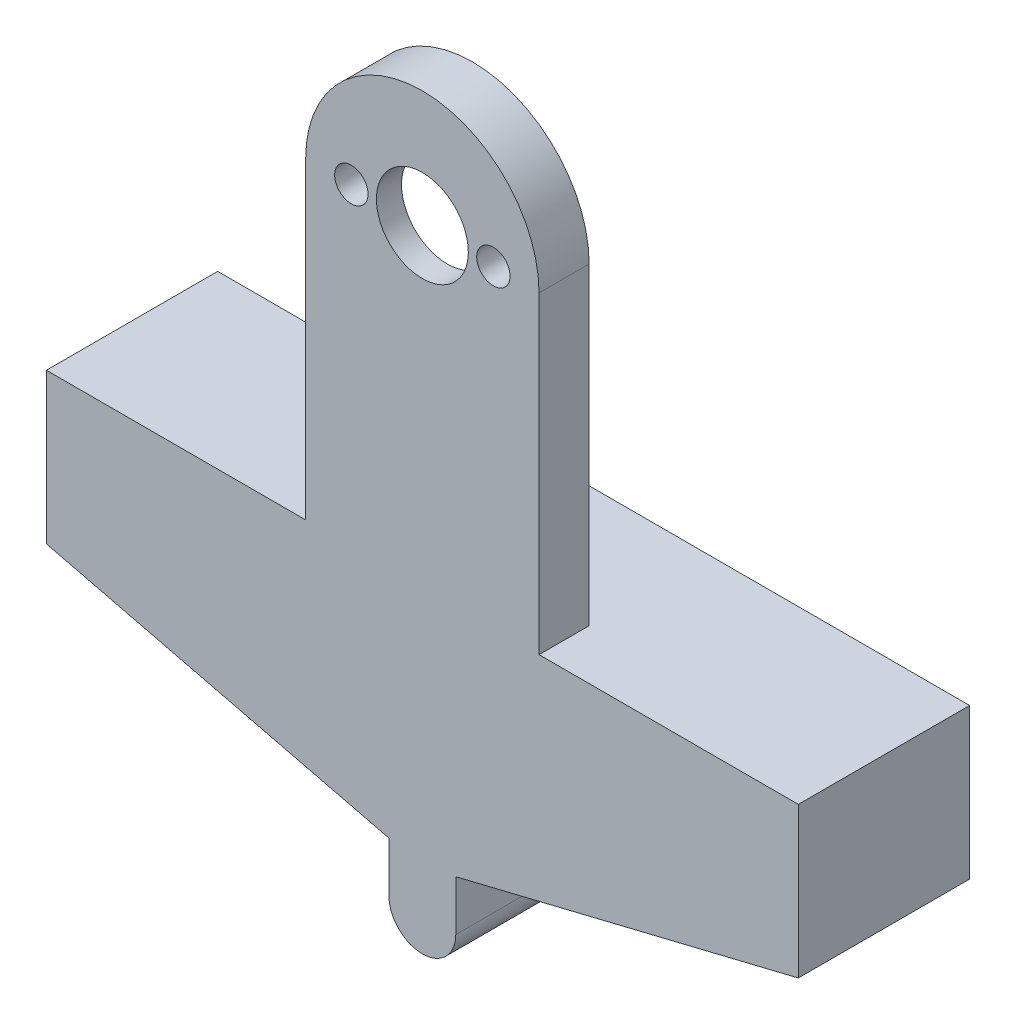
SolidWorks part; units mm, degrees
ref_plane "Front Plane" through (0, 0, 0) normal (0, 0, 1) x (1, 0, 0)
ref_plane "Top Plane" through (0, 0, 0) normal (0, 1, 0) x (1, 0, 0)
ref_plane "Right Plane" through (0, 0, 0) normal (1, 0, 0) x (0, 0, -1)
sketch "Sketch1" plane through (0, 0, 0) normal (0, 0, 1) x (1, 0, 0)
  line L0 (4, -9) -> (-4, -9)
  line L1 (-45, -9) -> (45, -9)
  line L2 (-45, -9) -> (-45, 9)
  line L3 (-45, 9) -> (45, 9)
  line L4 (45, -9) -> (45, 9)
  line L5 (-45, -9) -> (45, 9) construction
  line L6 (-45, 9) -> (45, -9) construction
  line L7 (-22.5, -3) -> (-7.5, -3)
  line L8 (-22.5, -3) -> (-22.5, 3)
  line L9 (-22.5, 3) -> (-7.5, 3)
  line L10 (-7.5, -3) -> (-7.5, 3)
  line L11 (-22.5, -3) -> (-7.5, 3) construction
  line L12 (-22.5, 3) -> (-7.5, -3) construction
  line L13 (7.5, -3) -> (22.5, -3)
  line L14 (7.5, -3) -> (7.5, 3)
  line L15 (7.5, 3) -> (22.5, 3)
  line L16 (22.5, -3) -> (22.5, 3)
  line L17 (7.5, -3) -> (22.5, 3) construction
  line L18 (7.5, 3) -> (22.5, -3) construction
  line L19 (4, -9) -> (4, -29)
  line L20 (-4, -9) -> (-4, -29)
  line L21 (4, -29) -> (-4, -29)
  line L22 (4, -19) -> (45, -9)
  line L23 (-4, -19) -> (-45, -9)
  point P0 (0, 0)
  point P6 (-15, 0)
  point P11 (15, 0)
  dimension "D1" = 90
  dimension "D2" = 18
  dimension "D3" = 6
  dimension "D4" = 6
  dimension "D5" = 6
  dimension "D6" = 6
  dimension "D7" = 15
  dimension "D8" = 15
  dimension "D9" = 7.5
  dimension "D10" = 7.5
  dimension "D11" = 8
  dimension "D12" = 4
  dimension "D13" = 20
extrude "Boss-Extrude1" add sketch "Sketch1" along normal blind 14 contours L1 L4 L3 L2 L0 L16 L13 L14 L15 L10 L7 L8 L9 | L21 L19 L0 L20 | L7 L10 L9 L8 | L13 L16 L15 L14 | L19 L22 L1 | L23 L20 L1 region at (0, -19, 0) region at (0, 0, 0) region at (17.6667, -12.3333, 0) region at (-17.6667, -12.3333, 0) region at (-15, 0, 0) region at (15, 0, 0)
sketch "Sketch3" plane through (0, 0, 0) normal (0, 0, 1) x (1, 0, 0)
  line L0 (4, -9) -> (-4, -9)
  line L1 (-45, -9) -> (45, -9)
  line L2 (-45, -9) -> (-45, 9)
  line L3 (-45, 9) -> (45, 9)
  line L4 (45, -9) -> (45, 9)
  line L5 (-45, -9) -> (45, 9) construction
  line L6 (-45, 9) -> (45, -9) construction
  line L7 (-22.5, -3) -> (-7.5, -3)
  line L8 (-22.5, -3) -> (-22.5, 3)
  line L9 (-22.5, 3) -> (-7.5, 3)
  line L10 (-7.5, -3) -> (-7.5, 3)
  line L11 (-22.5, -3) -> (-7.5, 3) construction
  line L12 (-22.5, 3) -> (-7.5, -3) construction
  line L13 (7.5, -3) -> (22.5, -3)
  line L14 (7.5, -3) -> (7.5, 3)
  line L15 (7.5, 3) -> (22.5, 3)
  line L16 (22.5, -3) -> (22.5, 3)
  line L17 (7.5, -3) -> (22.5, 3) construction
  line L18 (7.5, 3) -> (22.5, -3) construction
  line L19 (4, -9) -> (4, -29)
  line L20 (-4, -9) -> (-4, -29)
  line L21 (4, -29) -> (-4, -29)
  point P0 (0, 0)
  point P6 (-15, 0)
  point P11 (15, 0)
  dimension "D1" = 90
  dimension "D2" = 18
  dimension "D3" = 6
  dimension "D4" = 6
  dimension "D5" = 6
  dimension "D6" = 6
  dimension "D7" = 15
  dimension "D8" = 15
  dimension "D9" = 7.5
  dimension "D10" = 7.5
  dimension "D11" = 8
  dimension "D12" = 4
  dimension "D13" = 20
extrude "Boss-Extrude2" add sketch "Sketch3" against normal blind 6.5 contours L1 L4 L3 L2 L0 L16 L13 L14 L15 L10 L7 L8 L9 | L21 L19 L0 L20 region at (0, -19, 0) region at (0, 0, 0)
fillet "Fillet1" radius 4 2 edges at (-4, -29, 3.75) (4, -29, 3.75)
sketch "Sketch4" plane through (0, 0, 14) normal (0, 0, 1) x (1, 0, 0)
  line L0 (-13.9645, 46.5) -> (-13.9645, 9)
  line L1 (-45, 9) -> (45, 9) construction
  line L2 (13.9645, 46.5) -> (13.9645, 9)
  circle A0 centre (0, 46.5) radius 5.5
  circle A1 centre (8.5, 46.5) radius 2
  circle A2 centre (-8.5, 46.5) radius 2
  circle A3 centre (0, 46.5) radius 13.9645
  line M8 (45, 9) -> (-45, 9)
  dimension "D1" = 8.5
  dimension "D2" = 8.5
  dimension "D3" = 0
  dimension "D4" = 37.5
extrude "Boss-Extrude3" add sketch "Sketch4" against normal blind 6 contours A3 A0 A1 A2 | A3 L2 M8 | A3 L0 M8 region at (0, 22.4492, 14) region at (0, 60.0695, 14)
sketch "Sketch5" plane through (0, 0, 8) normal (0, 0, -1) x (-1, 0, 0)
  circle A2 centre (0, 46.5) radius 12.05
extrude "Cut-Extrude1" cut sketch "Sketch5" against normal blind 3
